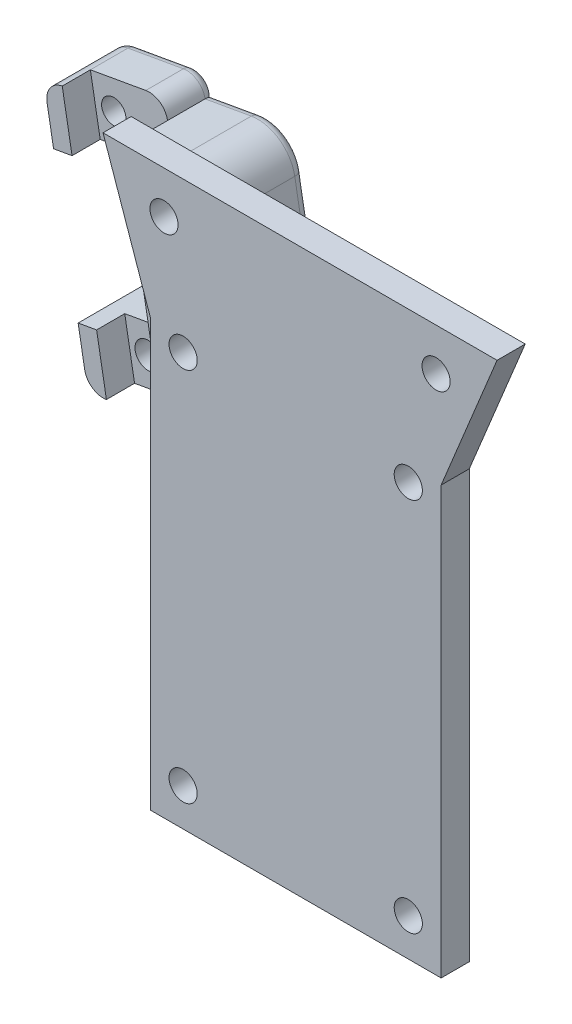
SolidWorks part; units mm, degrees
ref_plane "Front Plane" through (0, 0, 0) normal (0, 0, 1) x (1, 0, 0)
ref_plane "Top Plane" through (0, 0, 0) normal (0, 1, 0) x (1, 0, 0)
ref_plane "Right Plane" through (0, 0, 0) normal (1, 0, 0) x (0, 0, -1)
sketch "Sketch1" plane through (0, 0, 0) normal (0, 0, 1) x (1, 0, 0)
  line L1 (0, 0) -> (31, 0)
  line L2 (0, 0) -> (0, 45.5)
  line L3 (-5.037, 60) -> (36.963, 60)
  line L4 (31, 0) -> (31, 45.5)
  line L5 (36.963, 60) -> (31, 45.5)
  line L7 (-5.037, 60) -> (0, 45.5)
  circle A0 centre (30.463, 55.5) radius 1.5
  circle A1 centre (27.5, 44) radius 1.5
  circle A4 centre (27.5, 4) radius 1.5
  circle A5 centre (3.5, 4) radius 1.5
  circle A7 centre (3.5, 44) radius 1.5
  circle A9 centre (1.463, 55.5) radius 1.5
  point P29 (15.963, 60)
  dimension "D4" = 3
  dimension "D5" = 21
  dimension "D6" = 2
  dimension "D7" = 2
  dimension "D8" = 21
  dimension "D9" = 2.5
  dimension "D10" = 37
  dimension "D11" = 2.8
  dimension "D12" = 29
  dimension "D13" = 14.5
  dimension "D14" = 11.5
  dimension "D15" = 3
  dimension "D16" = 5
  dimension "D2" = 0
  dimension "D3" = 31
extrude "Boss-Extrude1" add sketch "Sketch1" along normal blind 3
sketch "Sketch3" plane through (0, 0, 0) normal (0, 0, -1) x (-1, 0, 0)
  line L0 (-5.4017, 56.1977) -> (-7.4387, 44.6977)
  line L2 (0.7257, 39.1892) -> (-4.1977, 40.0613)
  line L3 (-0.7653, 59.4387) -> (4.158, 58.5666)
  line L4 (4.158, 58.5666) -> (0.7257, 39.1892)
  line L5 (3.1733, 58.741) -> (-0.259, 39.3637) construction
  line L6 (0, 0) -> (0, 45.5)
  line L7 (0, 45.5) -> (5.037, 60)
  line L8 (5.037, 60) -> (-36.963, 60)
  line L9 (-36.963, 60) -> (-31, 45.5)
  line L10 (-31, 45.5) -> (-31, 0)
  line L11 (-31, 0) -> (0, 0)
  line L12 (0, 0) -> (0, 45.5) construction
  circle A0 centre (-1.463, 55.5) radius 1.5 construction
  circle A1 centre (-1.463, 55.5) radius 1.5 construction
  circle A2 centre (-1.463, 55.5) radius 2.6
  arc A3 (-0.7653, 59.4387) -> (-5.4017, 56.1977) centre (-1.463, 55.5) ccw
  circle A4 centre (-3.5, 44) radius 1.5 construction
  circle A5 centre (-3.5, 44) radius 1.5
  arc A6 (-7.4387, 44.6977) -> (-4.1977, 40.0613) centre (-3.5, 44) ccw
  dimension "D2" = 5.2
  dimension "D3" = 8
  dimension "D4" = 8
  dimension "D5" = 1
  dimension "D1" = 0
extrude "Boss-Extrude2" add sketch "Sketch3" along normal blind 5 separate body
sketch "Sketch6" plane through (0, 0, -5) normal (0, 0, -1) x (-1, 0, 0)
  line L0 (-6.4202, 50.4477) -> (2.4419, 48.8779)
  line L5 (0.7257, 39.1892) -> (4.158, 58.5666) construction
  line L8 (-5.4017, 56.1977) -> (-7.4387, 44.6977)
  line L9 (-4.1977, 40.0613) -> (0.7257, 39.1892)
  line L10 (0.7257, 39.1892) -> (4.158, 58.5666)
  line L11 (4.158, 58.5666) -> (-0.7653, 59.4387)
  line L12 (-5.4017, 56.1977) -> (-6.4202, 50.4477)
  line L14 (2.4419, 48.8779) -> (4.158, 58.5666)
  line L15 (4.158, 58.5666) -> (-0.7653, 59.4387)
  arc A2 (-0.7653, 59.4387) -> (-5.4017, 56.1977) centre (-1.463, 55.5) ccw
  arc A3 (-7.4387, 44.6977) -> (-4.1977, 40.0613) centre (-3.5, 44) ccw
  arc A4 (-0.7653, 59.4387) -> (-5.4017, 56.1977) centre (-1.463, 55.5) ccw
  circle A7 centre (-1.463, 55.5) radius 2.6 construction
  circle A8 centre (-1.463, 55.5) radius 2.6
  point P12 (2.4419, 48.8779)
  dimension "D1" = 0
extrude "Boss-Extrude5" add sketch "Sketch6" along normal blind 3
sketch "Sketch8" plane through (0, 0, -5) normal (0, 0, -1) x (-1, 0, 0)
  line L1 (-3.5, 40.75) -> (-0.6854, 42.375)
  line L6 (-0.6854, 42.375) -> (-0.6854, 45.625)
  line L7 (-0.6854, 45.625) -> (-3.5, 47.25)
  line L8 (-3.5, 47.25) -> (-6.3146, 45.625)
  line L9 (-6.3146, 45.625) -> (-6.3146, 42.375)
  line L10 (-6.3146, 42.375) -> (-3.5, 40.75)
  circle A0 centre (-3.5, 44) radius 2.8146 construction
  dimension "D2" = 6.5
  dimension "D1" = 5.6292
extrude "Cut-Extrude1" cut sketch "Sketch8" against normal blind 3
sketch "Sketch4" plane through (6.0268, 1.0675, 0) normal (-0.9847, -0.1744, 0) x (0, 0, 1)
  line L0 (0, 60.3941) -> (0, 33.3941)
  line L1 (0, 33.3941) -> (-8, 33.3941)
  line L2 (-8, 33.3941) -> (-8, 60.3941)
  line L3 (-8, 60.3941) -> (0, 60.3941)
  line L5 (0, 54.3941) -> (-4, 54.3941) construction
  line L6 (-8, 58.3941) -> (0, 58.3941) construction
  line L7 (0, 38.7151) -> (0, 58.3941) construction
  dimension "D1" = 27
  dimension "D2" = 4
  dimension "D3" = 4
  dimension "D4" = 6
  dimension "D5" = 8
extrude "Boss-Extrude7" add sketch "Sketch4" along normal blind 2
sketch "Sketch9" plane through (4.0574, 0.7187, 0) normal (-0.9847, -0.1744, 0) x (0, 0, 1)
  line L1 (-8, 60.3941) -> (-3, 60.3941)
  line L2 (-8, 60.3941) -> (-8, 54.3941)
  line L3 (-8, 54.3941) -> (-3, 54.3941)
  line L4 (-3, 60.3941) -> (-3, 54.3941)
  line L5 (-8, 33.3941) -> (-3, 33.3941)
  line L6 (-8, 33.3941) -> (-8, 39.3941)
  line L7 (-8, 39.3941) -> (-3, 39.3941)
  line L8 (-3, 33.3941) -> (-3, 39.3941)
  line L9 (0, 33.3941) -> (0, 60.3941) construction
  dimension "D1" = 6
  dimension "D2" = 3
  dimension "D3" = 3
  dimension "D4" = 6
extrude "Boss-Extrude8" add sketch "Sketch9" along normal blind 8
sketch "Sketch10" plane through (4.0574, 0.7187, 0) normal (-0.9847, -0.1744, 0) x (0, 0, 1)
  line L0 (0, -23.1) -> (0, 23.1) construction
  line L1 (-3, 55.3941) -> (0, 55.3941)
  line L2 (-3, 55.3941) -> (-3, 60.3941)
  line L3 (-3, 60.3941) -> (0, 60.3941)
  line L4 (0, 55.3941) -> (0, 60.3941)
  line L5 (0, 60.3941) -> (-3, 60.3941) construction
  line L6 (-3, 33.3941) -> (0, 33.3941) construction
  line L7 (-3, 38.3941) -> (0, 38.3941)
  line L8 (-3, 38.3941) -> (-3, 33.3941)
  line L9 (-3, 33.3941) -> (0, 33.3941)
  line L10 (0, 38.3941) -> (0, 33.3941)
  line L11 (-3, 33.3941) -> (-3, 39.3941) construction
  line L12 (-3, 54.3941) -> (-3, 60.3941) construction
  dimension "D1" = 5
  dimension "D2" = 5
extrude "Cut-Extrude2" cut sketch "Sketch10" against normal blind 2
sketch "Sketch11" plane through (0, 0, -3) normal (0, 0, 1) x (1, 0, 0)
  line L0 (-9.6444, 32.2057) -> (-10.6909, 38.1137) construction
  line L2 (-9.6444, 32.2057) -> (0.2024, 33.9498) construction
  line L3 (-14.3536, 58.7918) -> (-4.5068, 60.536) construction
  line L4 (-13.3071, 52.8838) -> (-14.3536, 58.7918) construction
  circle A0 centre (-6.2289, 35.8573) radius 1.4
  circle A1 centre (-9.8916, 56.5355) radius 1.3
  dimension "D3" = 2.8
  dimension "D4" = 2.6
  dimension "D1" = 4
  dimension "D2" = 3
  dimension "D5" = 3
  dimension "D6" = 4
extrude "Cut-Extrude3" cut sketch "Sketch11" against normal up to next (5 mm away)
sketch "Sketch12" plane through (0, 0, -3) normal (0, 0, 1) x (1, 0, 0)
  line L10 (-10.6909, 38.1137) -> (-9.6444, 32.2057)
  line L11 (-9.6444, 32.2057) -> (-7.675, 32.5545)
  line L12 (-9.6444, 32.2057) -> (0.2024, 33.9498) construction
  line L13 (-7.675, 32.5545) -> (-8.7215, 38.4625)
  line L14 (-10.6909, 38.1137) -> (-2.8135, 39.509) construction
  line L15 (-8.7215, 38.4625) -> (-10.6909, 38.1137)
  line L16 (-14.3536, 58.7918) -> (-13.3071, 52.8838)
  line L17 (-13.3071, 52.8838) -> (-11.3377, 53.2326)
  line L18 (-13.3071, 52.8838) -> (-5.4297, 54.2791) construction
  line L19 (-11.3377, 53.2326) -> (-12.3842, 59.1406)
  line L20 (-14.3536, 58.7918) -> (-4.5068, 60.536) construction
  line L21 (-12.3842, 59.1406) -> (-14.3536, 58.7918)
  dimension "D1" = 2
  dimension "D2" = 2
extrude "Boss-Extrude9" add sketch "Sketch12" along normal up to vertex (3 mm away)
fillet "Fillet1" radius 2 4 edges at (-1.5838, 44.0336, -5) (1.9892, 49.6628, -5) (-4.5068, 60.536, -5.5) (0.2024, 33.9498, -5.5)
fillet "Fillet2" radius 1 19 edges at (3.7548, 58.7784, -8) (-1.6963, 59.0027, -8) (-1.2942, 42.3985, -8) (-9.4302, 59.6639, -8) (-4.1216, 46.8941, -8) (-13.6559, 54.8531, -8) (-9.3684, 53.5814, -8) (-6.7522, 38.8114, -8) (-10.342, 36.1443, -8) (-4.721, 33.0777, -8) (1.9892, 49.6628, -8) (5.9109, 53.3227, -8) (-13.6746, 58.3172, -8) (-9.1697, 32.8846, -8) (-0.4766, 34.4244, -8) (-4.9815, 59.857, -8) (-1.137, 55.5, -8) (-11.1916, 56.5355, -8) (-7.6289, 35.8573, -8)
